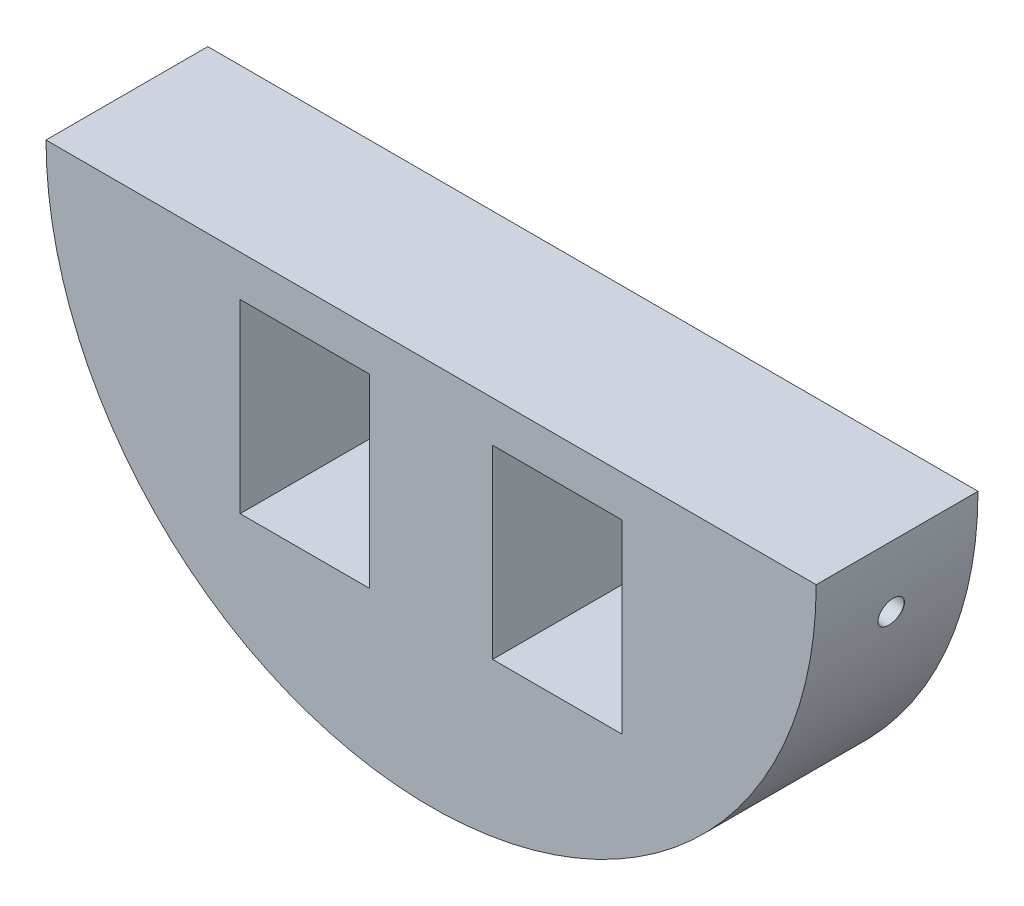
SolidWorks part; units mm, degrees
ref_plane "Front Plane" through (0, 0, 0) normal (0, 0, 1) x (1, 0, 0)
ref_plane "Top Plane" through (0, 0, 0) normal (0, 1, 0) x (1, 0, 0)
ref_plane "Right Plane" through (0, 0, 0) normal (1, 0, 0) x (0, 0, -1)
sketch "Sketch1" plane through (0, 0, 0) normal (0, 0, 1) x (1, 0, 0)
  line L0 (-119, 0) -> (0, 0)
  line L3 (-50, -35) -> (-30, -35)
  line L4 (-50, -35) -> (-50, -15)
  line L5 (-50, -15) -> (-30, -15)
  line L6 (-30, -35) -> (-30, -15)
  line L7 (-89, -35) -> (-69, -35)
  line L8 (-89, -35) -> (-89, -15)
  line L9 (-89, -15) -> (-69, -15)
  line L10 (-69, -35) -> (-69, -15)
  arc A1 (-119, 0) -> (0, 0) centre (-59.5, 0) ccw
  dimension "D1" = 30
  dimension "D7" = 59.5
  dimension "D2" = 15
  dimension "D3" = 30
  dimension "D4" = 20
extrude "Boss-Extrude1" add sketch "Sketch1" along normal blind 25
hole_wizard "Ø4.0mm Dowel Hole2" positions "3DSketch2" profile "Sketch4" hole size "Ø4.0" standard "ANSI Metric"
sketch3d "3DSketch2"
  line L2 (0, 0, 25) -> (0, 0, 0) construction
  line L4 (0, 0, 25) -> (0, 0, 0) construction
  line L5 (0, 0, 12.5) -> (-0.9039, -10.3321, 12.5) construction
  line L8 (-59.5, 0, 0) -> (-59.5, 0, 25) construction
  line L9 (0, 0, 0) -> (-119, 0, 0) construction
  line L10 (0, 0, 25) -> (-119, 0, 25) construction
  line L12 (-59.5, 0, 12.5) -> (-0.9039, -10.3321, 12.5) construction
  line L16 (-59.5, 0, 12.5) -> (0, 0, 12.5) construction
  point P0 (-0.9039, -10.3321, 12.5)
  point P16 (-0.9039, -10.3321, 12.5)
  point P23 (-0.9039, -10.3321, 12.5)
  point P25 (-0.9039, -10.3321, 12.5)
  dimension "D1" = 10
sketch "Sketch4" plane through (-0.9039, -10.3321, 12.5) normal (0, 0, 1) x (0.1736, 0.9848, 0)
  line L0 (0, 0) -> (0, 11.2017)
  line L1 (0, 11.2017) -> (2, 10)
  line L2 (2, 10) -> (2, 0.025)
  line L3 (2, 0.025) -> (2.025, 0)
  line L5 (2.025, 0) -> (0, 0)
  line L6 (-2, 0.025) -> (-2.025, 0) construction
  line L10 (0, 11.2017) -> (-2, 10) construction
  line L11 (0, -6.35) -> (0, 107.95) construction
  dimension "Hole Dia." = 4
  dimension "Hole Depth" = 10
  dimension "Near C'Sink Dia." = 4.05
  dimension "Near C'Sink Angle" = 90
  dimension "Drill Angle" = 118
pattern_circular "CirPattern1" count 5 over 160 about axis through (-59.5, 0, 0) along (0, 0, 1) of "Ø4.0mm Dowel Hole2" reverse direction yes
chamfer "Chamfer1" distance 15 angle 30 2 edges at (-79, -15, 25) (-40, -15, 25) first distance on face at (-79, -15, 12.5) first distance on face at (-40, -15, 12.5)
